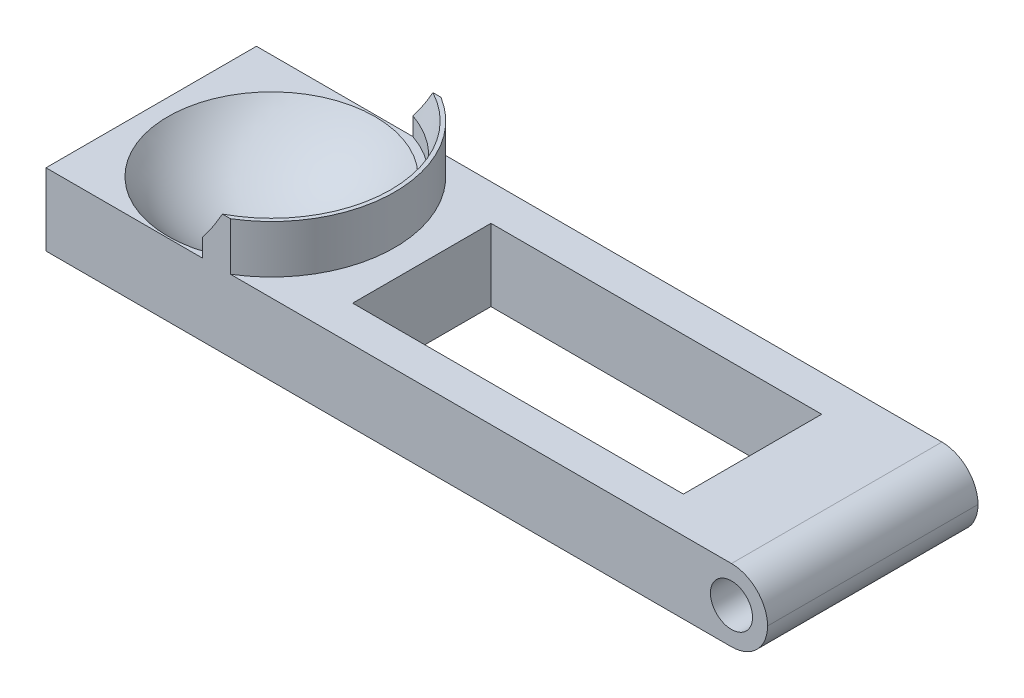
SolidWorks part; units mm, degrees
ref_plane "Front" through (0, 0, 0) normal (0, 0, 1) x (1, 0, 0)
ref_plane "Top" through (0, 0, 0) normal (0, 1, 0) x (1, 0, 0)
ref_plane "Right" through (0, 0, 0) normal (1, 0, 0) x (0, 0, -1)
sketch "Sketch1" plane through (0, 0, 0) normal (0, 1, 0) x (1, 0, 0)
  line L1 (-60, 17.5) -> (60, 17.5)
  line L2 (-60, 17.5) -> (-60, -17.5)
  line L3 (-60, -17.5) -> (60, -17.5)
  line L4 (60, 17.5) -> (60, -17.5)
  line L5 (-60, 17.5) -> (60, -17.5) construction
  line L6 (-60, -17.5) -> (60, 17.5) construction
  point P0 (0, 0)
  dimension "D1" = 35
  dimension "D2" = 120
extrude "Boss-Extrude1" add sketch "Sketch1" along normal mid plane 12
fillet "Fillet1" radius 6 2 edges at (60, 6, 0) (60, -6, 0)
sketch "Sketch2" plane through (0, 0, 0) normal (0, 0, 1) x (1, 0, 0)
  line L0 (-60, 6) -> (-60, -6) construction
  line L1 (-60, 6) -> (54, 6) construction
  line L2 (-61, 18) -> (-19, 18)
  arc A0 (-19, 18) -> (-61, 18) centre (-40, 18) ccw
  dimension "D1" = 42
  dimension "D2" = 20
  dimension "D3" = 12
revolve "Cut-Revolve1" cut sketch "Sketch2" angle 360 about L2
hole_wizard "Ø6.0mm Dowel Hole1" positions "Sketch3" profile "Sketch4" hole size "Ø6.0" standard "ANSI Metric" end condition through all
sketch "Sketch3" plane through (0, 0, 17.5) normal (0, 0, 1) x (1, 0, 0)
  point P0 (54, 0)
sketch "Sketch4" plane through (54, 0, 17.5) normal (1, 0, 0) x (0, -1, 0)
  line L0 (0, 0) -> (0, 35)
  line L1 (0, 35) -> (3.5, 35)
  line L2 (3.5, 35) -> (3.5, 0)
  line L5 (3.5, 0) -> (0, 0)
  line L11 (0, -6.35) -> (0, 107.95) construction
  dimension "Thru Hole Dia." = 7
  dimension "Thru Hole Depth" = 35
sketch "Sketch5" plane through (0, -6, 0) normal (0, -1, 0) x (1, 0, 0)
  line L0 (-60, 17.5) -> (54, 17.5) construction
  line L1 (-60, -17.5) -> (-60, 17.5) construction
  line L2 (50, 0) -> (-50, 0) construction
  circle A0 centre (-45.5, 10) radius 5.25
  circle A1 centre (-45.5, -10) radius 5.25
  dimension "D1" = 10.5
  dimension "D2" = 7.5
  dimension "D3" = 14.5
extrude "Cut-Extrude1" cut sketch "Sketch5" against normal blind 1.5
sketch "Sketch6" plane through (0, 6, 0) normal (0, 1, 0) x (1, 0, 0)
  line L0 (-60, 17.5) -> (-60, -17.5) construction
  line L1 (-15, 11.5) -> (40, 11.5)
  line L2 (-15, 11.5) -> (-15, -11.5)
  line L3 (-15, -11.5) -> (40, -11.5)
  line L4 (40, 11.5) -> (40, -11.5)
  point P6 (-15, 0)
  dimension "D1" = 45
  dimension "D2" = 55
  dimension "D3" = 23
extrude "Cut-Extrude2" cut sketch "Sketch6" against normal through all
sketch "Sketch7" [suppressed] plane through (0, 7.5, 0) normal (0, 1, 0) x (1, 0, 0)
  line L1 (40, -7.4525) -> (40, -11.4525)
  line L3 (-15, -7.4525) -> (-4.0577, 11.5)
  line L5 (-15, 11.5) -> (-15, -11.5) construction
  line L13 (40, 11.5) -> (-15, 11.5) construction
  line L14 (-4.0577, 11.5) -> (-0.3077, 11.5)
  line L15 (-0.3077, 11.5) -> (11.8166, -9.5)
  line L16 (11.8166, -9.5) -> (13.1834, -9.5)
  line L22 (13.1834, -9.5) -> (25.3077, 11.5)
  line L23 (25.3077, 11.5) -> (29.0577, 11.5)
  line L24 (29.0577, 11.5) -> (40, -7.4525)
  line L25 (40, -11.5) -> (40, 11.5) construction
  line L28 (-15, -11.5) -> (40, -11.5) construction
  line L30 (26.4624, 9.5) -> (14.3381, -11.5)
  line L31 (14.3381, -11.5) -> (10.6619, -11.5)
  line L32 (10.6619, -11.5) -> (-1.4624, 9.5)
  line L35 (-15, -11.4525) -> (-15, -7.4525)
  line L36 (26.4624, 9.5) -> (27.903, 9.5)
  line L37 (27.903, 9.5) -> (40, -11.4525)
  line L38 (-1.4624, 9.5) -> (-2.903, 9.5)
  line L39 (-2.903, 9.5) -> (-15, -11.4525)
  point P6 (-2.1827, 9.5)
  point P16 (40, -10.3689)
  point P17 (13.5004, -9.5)
  point P24 (0, 0)
  point P26 (40, -10.3689)
  point P27 (40, -10.3689)
  point P30 (-2.1827, 11.5)
  point P31 (27.1827, 11.5)
  point P32 (27.1827, 9.5)
  point P33 (-15, -10.3689)
  point P34 (12.5, -11.5)
  point P35 (12.5, -11.5)
  point P36 (-1.4624, 9.5)
  point P37 (0, 0)
  dimension "D1" = 60
  dimension "D2" = 60
  dimension "D3" = 60
  dimension "D4" = 60
  dimension "D5" = 2
  dimension "D6" = 2
  dimension "D7" = 2
  dimension "D8" = 2
  dimension "D9" = 2
  dimension "D10" = 3.75
  dimension "D11" = 3.75
sketch "Sketch8" plane through (0, 6, 0) normal (0, 1, 0) x (1, 0, 0)
  line L0 (-34, 17.5) -> (-29.3229, 17.5)
  line L1 (-34, -17.5) -> (-29.3229, -17.5)
  line L2 (-60, -17.5) -> (54, -17.5) construction
  line L3 (54, 17.5) -> (-60, 17.5) construction
  arc A0 (-29.3229, -17.5) -> (-29.3229, 17.5) centre (-40, 0) ccw
  arc A1 (-34, -17.5) -> (-34, 17.5) centre (-40, 0) ccw
  circle A2 centre (-40, 0) radius 17.2337 construction
  point P1 (0, 0)
  dimension "D1" = 20.5
  dimension "D2" = 18.5
extrude "Boss-Extrude4" add sketch "Sketch8" along normal blind 8
chamfer "Chamfer1" distance 5 angle 15 1 edges at (-21.5, 14, 0) first distance on face at (-27.75, 10, 0)
